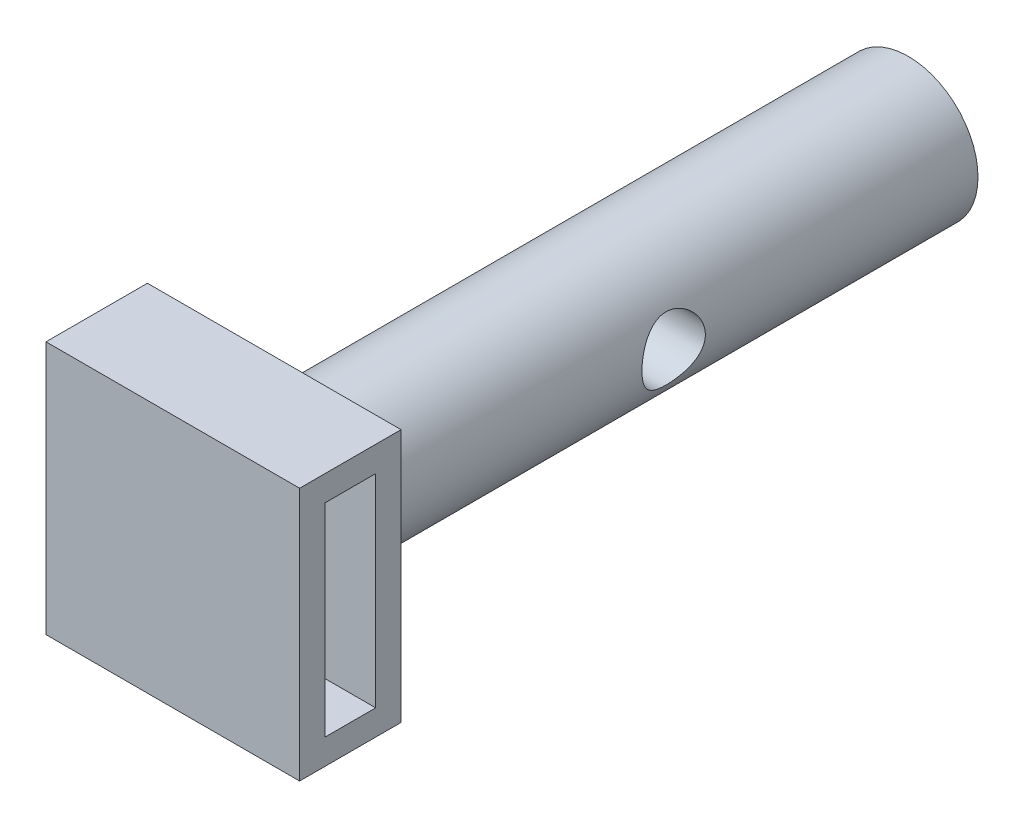
SolidWorks part; units mm, degrees
ref_plane "Front Plane" through (0, 0, 0) normal (0, 0, 1) x (1, 0, 0)
ref_plane "Top Plane" through (0, 0, 0) normal (0, 1, 0) x (1, 0, 0)
ref_plane "Right Plane" through (0, 0, 0) normal (1, 0, 0) x (0, 0, -1)
sketch "Sketch2" plane through (0, 0, 0) normal (0, 0, 1) x (1, 0, 0)
  circle A4 centre (0, 0) radius 2.75
  point P3 (25, 0)
  dimension "D1" = 5.5
ref_plane "Plane1" through (0, 0, 25) normal (0, 0, 1) x (1, 0, 0)
sketch "Sketch3" plane through (0, 0, 25) normal (0, 0, 1) x (1, 0, 0)
  line L0 (-5, 5) -> (5, 5)
  line L1 (-5, 5) -> (-5, -5)
  line L2 (-5, -5) -> (5, -5)
  line L3 (5, 5) -> (5, -5)
  circle A0 centre (0, 0) radius 2.75
  point P3 (0, 5)
  point P9 (5, 0)
  dimension "D1" = 5.5
  dimension "D2" = 10
loft "Loft1" add profiles "Sketch2", "Sketch3" connector at (0.2399, 2.7395, 0) connector at (0.0916, 2.7485, 25)
extrude "Boss-Extrude4" add sketch "Sketch3<7>" along normal blind 4 contours A0 L3 L0 L1 | A0 L1 L2 L3 | A0 | A0 L0 L1 | A0 L2 L3 region at (0, 4.8586, 25) region at (0, 0, 25)
sketch "Sketch3<7>" plane through (0, 0, 25) normal (0, 0, 1) x (1, 0, 0) same geometry as "Sketch3"
sketch "Sketch8" plane through (5, 0, 0) normal (1, 0, 0) x (0, 0, -1)
  line L0 (-29, 5) -> (-29, -5) construction
  line L1 (-28, 4) -> (-26, 4)
  line L2 (-28, 4) -> (-28, -4)
  line L3 (-28, -4) -> (-26, -4)
  line L4 (-26, 4) -> (-26, -4)
  line L5 (-29, 5) -> (-25, 5) construction
  point P4 (-28, 0)
  point P7 (-29, 0)
  point P8 (-27, 4)
  point P11 (-27, 5)
  dimension "D1" = 2
  dimension "D2" = 8
extrude "Cut-Extrude2" cut sketch "Sketch8" against normal through all both and the other way through all
fillet "Fillet1" radius 1 1 edges at (2.75, 0, 25)
ref_plane "Plane2" [suppressed] through (-3.4151, 5.9151, 0) normal (0.5, -0.866, 0) x (0, 0, -1)
ref_plane "Plane3" [suppressed] through (2.9244, -5.0652, 0) normal (0.5, -0.866, 0) x (0, 0, -1)
sketch "Sketch10" [suppressed] plane through (2.9244, -5.0652, 0) normal (0.5, -0.866, 0) x (0, 0, -1)
  line L1 (-15.5, -3.25) -> (0, -3.25) construction
  circle A0 centre (-16.5644, -7) radius 1.25
  dimension "D1" = 7
  dimension "D3" = 2.5
  dimension "D2" = 3.75
extrude "Cut-Extrude3" [suppressed] cut sketch "Sketch10" against normal blind 3 from surface contours A0 starting at face at (2.75, 0, 24)
mirror "Mirror1" [suppressed] about plane through (0, 0, 0) normal (1, 0, 0)
sketch "Sketch11" plane through (0, 0, 0) normal (1, 0, 0) x (0, 0, -1)
  line L1 (0, 0) -> (-24, 0) construction
  line L2 (0, -2.75) -> (0, 2.75) construction
  line L3 (-24, -2.75) -> (-24, 2.75) construction
  circle A0 centre (-12, 0) radius 1.25
  dimension "D1" = 2.5
extrude "Cut-Extrude4" cut sketch "Sketch11" against normal through all both and the other way through all
